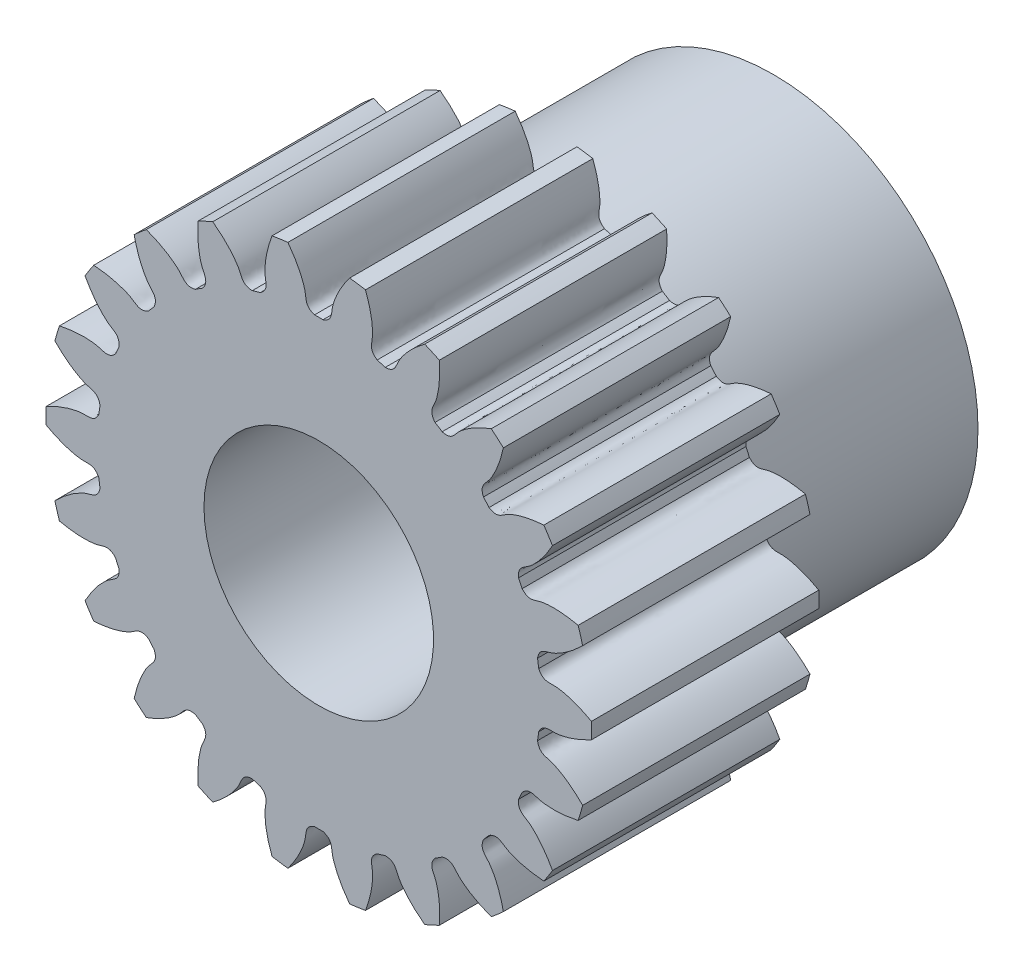
SolidWorks part; units mm, degrees
ref_plane "前视基准面" through (0, 0, 0) normal (0, 0, 1) x (1, 0, 0)
ref_plane "上视基准面" through (0, 0, 0) normal (0, 1, 0) x (1, 0, 0)
ref_plane "右视基准面" through (0, 0, 0) normal (1, 0, 0) x (0, 0, -1)
sketch "草图1" plane through (0, 0, 0) normal (0, 0, 1) x (1, 0, 0)
  circle A0 centre (0, 0) radius 12
extrude "凸台-拉伸1" add sketch "草图1" along normal blind 10
ref_axis "基准轴1" through (0, 0, -0.5) along (0, 0, 1)
sketch "草图2" plane through (0, 0, 0) normal (0, 0, 1) x (1, 0, 0)
  line L0 (0, 0) -> (0, 12) construction
  circle A0 centre (0, 0) radius 12 construction
  arc A1 (0.1857, 9.7482) -> (-0.1857, 9.7482) centre (0, 0) ccw
  arc A2 (3.0856, 13.5599) -> (-3.0856, 13.5599) centre (0, 0) ccw
  spline S0 degree 3 poles (0.1857, 9.7482) (0.5882, 9.8762) (0.5483, 10.1518) (0.5996, 10.4216) (0.606, 10.4519) (0.6139, 10.4862) (0.6235, 10.5243) (0.6349, 10.5661) (0.6484, 10.6117) (0.664, 10.661) (0.6819, 10.7139) (0.7023, 10.7703) (0.7253, 10.8301) (0.7511, 10.8933) (0.7797, 10.9597) (0.8114, 11.0293) (0.8462, 11.1021) (0.8843, 11.1778) (0.9259, 11.2563) (0.9711, 11.3377) (1.0199, 11.4217) (1.0726, 11.5082) (1.1292, 11.5972) (1.1899, 11.6884) (1.2547, 11.7818) (1.3238, 11.8773) (1.3973, 11.9746) (1.4753, 12.0737) (1.5579, 12.1744) (1.6452, 12.2766) (1.7372, 12.3802) (1.8341, 12.4849) (1.9359, 12.5906) (2.0428, 12.6972) (2.1547, 12.8044) (2.2718, 12.9123) (2.3942, 13.0205) (2.5218, 13.1289) (2.6548, 13.2373) (2.8415, 13.3834) (2.9864, 13.49) (3.0856, 13.5599) knots 0 0 0 0 0.157021 0.162531 0.168888 0.176093 0.184146 0.193046 0.202794 0.213389 0.224833 0.237123 0.250262 0.264248 0.279082 0.294763 0.311292 0.328669 0.346893 0.365965 0.385884 0.406652 0.428266 0.450729 0.474039 0.498197 0.523202 0.549055 0.575756 0.603304 0.6317 0.660944 0.691035 0.721974 0.75376 0.786395 0.819876 0.854206 0.889383 0.925408 1 1 1 1
  spline S1 degree 3 poles (-0.1857, 9.7482) (-0.5882, 9.8762) (-0.5483, 10.1518) (-0.5996, 10.4216) (-0.606, 10.4519) (-0.6139, 10.4862) (-0.6235, 10.5243) (-0.6349, 10.5661) (-0.6484, 10.6117) (-0.664, 10.661) (-0.6819, 10.7139) (-0.7023, 10.7703) (-0.7253, 10.8301) (-0.7511, 10.8933) (-0.7797, 10.9597) (-0.8114, 11.0293) (-0.8462, 11.1021) (-0.8843, 11.1778) (-0.9259, 11.2563) (-0.9711, 11.3377) (-1.0199, 11.4217) (-1.0726, 11.5082) (-1.1292, 11.5972) (-1.1899, 11.6884) (-1.2547, 11.7818) (-1.3238, 11.8773) (-1.3973, 11.9746) (-1.4753, 12.0737) (-1.5579, 12.1744) (-1.6452, 12.2766) (-1.7372, 12.3802) (-1.8341, 12.4849) (-1.9359, 12.5906) (-2.0428, 12.6972) (-2.1547, 12.8044) (-2.2718, 12.9123) (-2.3942, 13.0205) (-2.5218, 13.1289) (-2.6548, 13.2373) (-2.8415, 13.3834) (-2.9864, 13.49) (-3.0856, 13.5599) knots 0 0 0 0 0.157021 0.162531 0.168888 0.176093 0.184146 0.193046 0.202794 0.213389 0.224833 0.237123 0.250262 0.264248 0.279082 0.294763 0.311292 0.328669 0.346893 0.365965 0.385884 0.406652 0.428266 0.450729 0.474039 0.498197 0.523202 0.549055 0.575756 0.603304 0.6317 0.660944 0.691035 0.721974 0.75376 0.786395 0.819876 0.854206 0.889383 0.925408 1 1 1 1
extrude "切除-拉伸1" cut sketch "草图2" along normal through all
pattern_circular "阵列(圆周)1" count 22 every 16.364 about axis through (0, 0, -0.5) along (0, 0, 1) of "切除-拉伸1"
sketch "草图3" plane through (0, 0, 0) normal (0, 0, 1) x (1, 0, 0)
  circle A0 centre (0, 0) radius 11 construction
  dimension "Dn" = 22
sketch "草图4" plane through (0, 0, 0) normal (0, 0, 1) x (1, 0, 0)
  circle A0 centre (0, 0) radius 9
  dimension "D1" = 18
extrude "凸台-拉伸2" add sketch "草图4" against normal blind 10
sketch "草图5" plane through (0, 0, -10) normal (0, 0, -1) x (-1, 0, 0)
  circle A0 centre (0, 0) radius 5.05
  dimension "D1" = 10.1
extrude "切除-拉伸2" cut sketch "草图5" against normal through all
